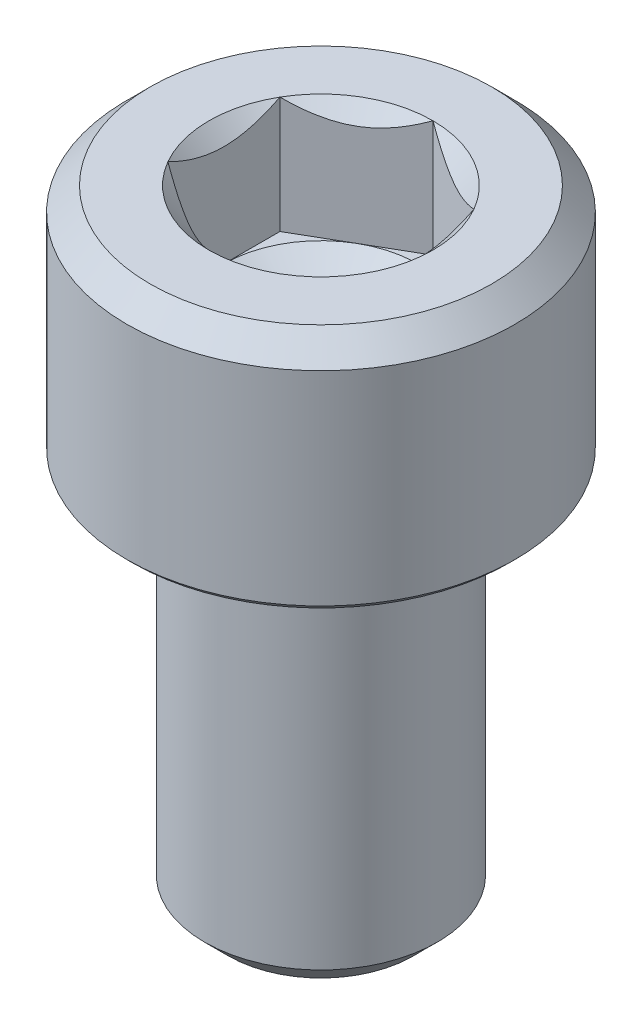
SolidWorks part; units mm, degrees
ref_plane "Front Plane" through (0, 0, 0) normal (0, 0, 1) x (1, 0, 0)
ref_plane "Top Plane" through (0, 0, 0) normal (0, 1, 0) x (1, 0, 0)
ref_plane "Right Plane" through (0, 0, 0) normal (1, 0, 0) x (0, 0, -1)
sketch "Sketch1" plane through (0, 0, 0) normal (0, 0, 1) x (1, 0, 0)
  line L0 (0, 1.5566) -> (2.5, 3)
  line L1 (2.5, 3) -> (2.5, 5.6132)
  line L2 (2.5, 5.6132) -> (2.8868, 6)
  line L3 (2.8868, 6) -> (4.4, 6)
  line L4 (4.4, 6) -> (5, 5.4)
  line L5 (5, 5.4) -> (5, 0.15)
  line L6 (5, 0.15) -> (4.85, 0)
  line L7 (4.85, 0) -> (3.05, 0)
  line L8 (3.05, 0) -> (3, -0.68)
  line L9 (3, -0.68) -> (3, -9.3865)
  line L10 (3, -9.3865) -> (2.3865, -10)
  line L11 (2.3865, -10) -> (0, -10)
  line L12 (0, -10) -> (0, 1.5566)
  line L13 (0, -10) -> (0, 6) construction
revolve "Revolve1" add sketch "Sketch1" angle 360 about L13 reverse direction yes
cosmetic thread "Cosmetic Thread1" parameters "D1"=7, "D2"=4.773
ref_plane "Plane1" through (0, 6, 0) normal (0, 1, 0) x (1, 0, 0)
sketch "Sketch2" plane through (0, 6, 0) normal (0, 1, 0) x (1, 0, 0)
  line L0 (-2.5, -1.4434) -> (0, -2.8868)
  line L1 (0, -2.8868) -> (2.5, -1.4434)
  line L2 (2.5, -1.4434) -> (2.5, 1.4434)
  line L3 (2.5, 1.4434) -> (0, 2.8868)
  line L4 (0, 2.8868) -> (-2.5, 1.4434)
  line L5 (-2.5, 1.4434) -> (-2.5, -1.4434)
extrude "Cut-Extrude1" cut sketch "Sketch2" against normal blind 3
ref_plane "Plane2" through (0, -10, 0) normal (0, 1, 0) x (1, 0, 0)
ref_plane "ANBAU XY" through (0, 0, 0) normal (0, 1, 0) x (1, 0, 0)
ref_plane "ANBAU XZ" through (0, 0, 0) normal (0, 0, 1) x (1, 0, 0)
ref_plane "ANBAU YZ" through (0, 0, 0) normal (1, 0, 0) x (0, 0, -1)
ref_axis "ANBAU X" through (-80.9, 0, 0) along (1, 0, 0)
ref_axis "ANBAU Y" through (0, 0, 50) along (0, 0, -1)
ref_axis "ANBAU Z" through (0, 50, 0) along (0, -1, 0)
sketch3d "ANBAU"
  point P0 (0, 0, 0)
ref_plane "Schraube XY" through (0, 0, 0) normal (0, 1, 0) x (1, 0, 0)
ref_plane "Schraube XZ" through (0, 0, 0) normal (0, 0, 1) x (1, 0, 0)
ref_plane "Schraube YZ" through (0, 0, 0) normal (1, 0, 0) x (0, 0, -1)
ref_axis "Schraube X" through (-80.9, 0, 0) along (1, 0, 0)
ref_axis "Schraube Y" through (0, 0, 50) along (0, 0, -1)
ref_axis "Schraube Z" through (0, 50, 0) along (0, -1, 0)
sketch3d "Schraube"
  point P0 (0, 0, 0)
ref_plane "insert XY" through (0, 0, 0) normal (0, 1, 0) x (1, 0, 0)
ref_plane "insert XZ" through (0, 0, 0) normal (0, 0, 1) x (1, 0, 0)
ref_plane "insert YZ" through (0, 0, 0) normal (1, 0, 0) x (0, 0, -1)
ref_axis "insert X" through (-80.9, 0, 0) along (1, 0, 0)
ref_axis "insert Y" through (0, 0, 50) along (0, 0, -1)
ref_axis "insert Z" through (0, 50, 0) along (0, -1, 0)
sketch3d "insert"
  point P0 (0, 0, 0)
ref_plane "schrauben_punkt XY" through (0, -10, 0) normal (0, 1, 0) x (1, 0, 0)
ref_plane "schrauben_punkt XZ" through (0, 0, 0) normal (0, 0, 1) x (1, 0, 0)
ref_plane "schrauben_punkt YZ" through (0, 0, 0) normal (1, 0, 0) x (0, 0, -1)
ref_axis "schrauben_punkt X" through (-80.9, -10, 0) along (1, 0, 0)
ref_axis "schrauben_punkt Y" through (0, -10, 50) along (0, 0, -1)
ref_axis "schrauben_punkt Z" through (0, 50, 0) along (0, -1, 0)
sketch3d "schrauben_punkt"
  point P0 (0, -10, 0)
other "Freeze***"
